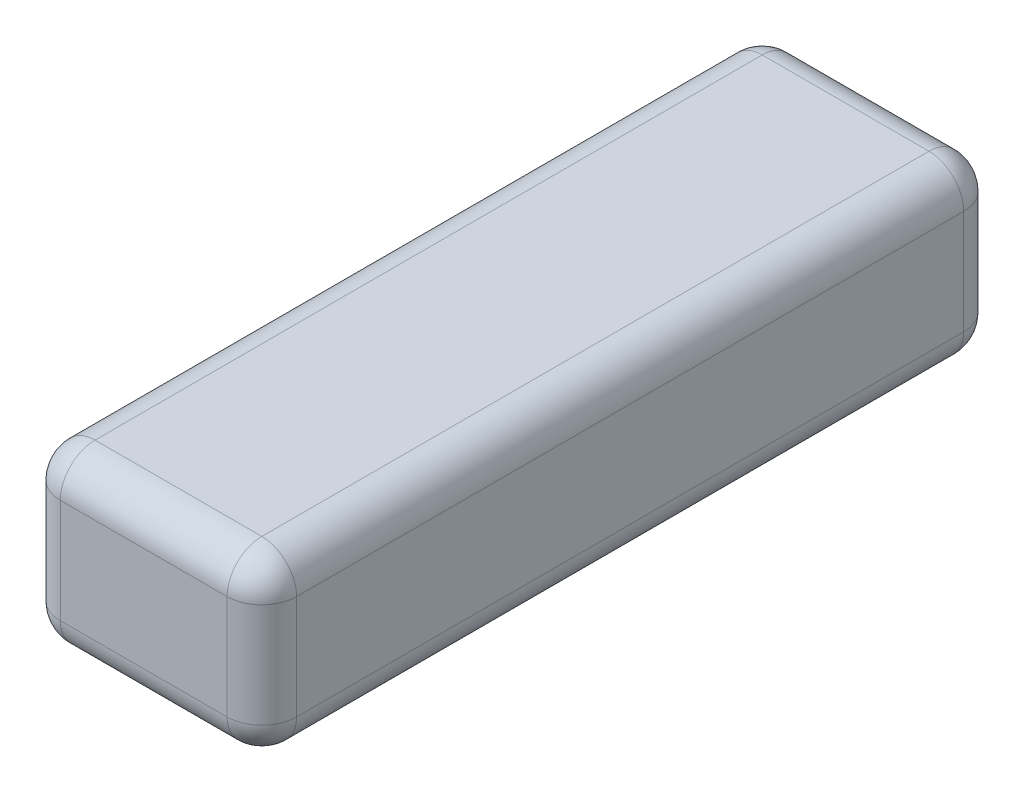
SolidWorks part; units mm, degrees
ref_plane "Plan de face" through (0, 0, 0) normal (0, 0, 1) x (1, 0, 0)
ref_plane "Plan de dessus" through (0, 0, 0) normal (0, 1, 0) x (1, 0, 0)
ref_plane "Plan de droite" through (0, 0, 0) normal (1, 0, 0) x (0, 0, -1)
sketch "Esquisse1" plane through (0, 0, 0) normal (0, 1, 0) x (1, 0, 0)
  line L1 (-17, -53) -> (17, -53)
  line L2 (-17, -53) -> (-17, 53)
  line L3 (-17, 53) -> (17, 53)
  line L4 (17, -53) -> (17, 53)
  line L5 (-17, -53) -> (17, 53) construction
  line L6 (-17, 53) -> (17, -53) construction
  point P0 (0, 0)
  dimension "D1" = 106
  dimension "D2" = 34
extrude "Boss.-Extru.1" add sketch "Esquisse1" along normal blind 12.5 and the other way blind 12.5
fillet "Congé1" radius 5 4 edges at (17, 0, -53) (-17, 0, -53) (-17, 0, 53) (17, 0, 53)
fillet "Congé2" radius 5 16 edges at (17, -12.5, 0) (15.5355, -12.5, -51.5355) (0, -12.5, -53) (-15.5355, -12.5, -51.5355) (-17, -12.5, 0) (-15.5355, -12.5, 51.5355) (0, -12.5, 53) (0, 12.5, 53) (-15.5355, 12.5, 51.5355) (-17, 12.5, 0) (-15.5355, 12.5, -51.5355) (0, 12.5, -53) (15.5355, 12.5, -51.5355) (17, 12.5, 0) (15.5355, -12.5, 51.5355) (15.5355, 12.5, 51.5355)
